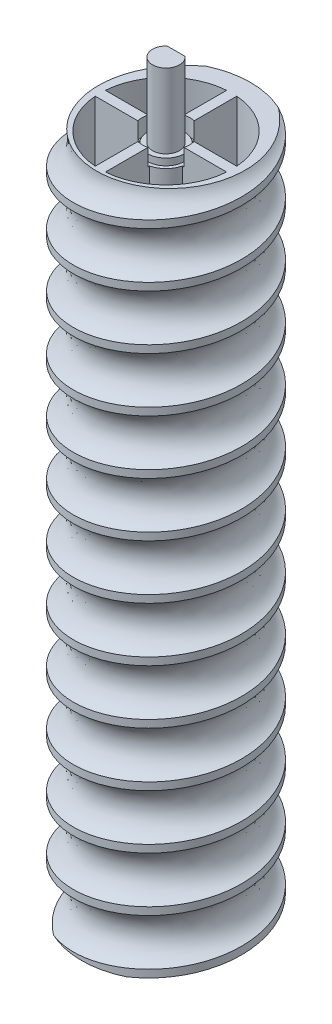
SolidWorks part; units mm, degrees
material "PMMA"
ref_plane "Front Plane" through (0, 0, 0) normal (0, 0, 1) x (1, 0, 0)
ref_plane "Top Plane" through (0, 0, 0) normal (0, 1, 0) x (1, 0, 0)
ref_plane "Right Plane" through (0, 0, 0) normal (1, 0, 0) x (0, 0, -1)
sketch "Sketch1" plane through (0, 0, 0) normal (0, 1, 0) x (1, 0, 0)
  circle A0 centre (0, 0) radius 25
  dimension "D1" = 50
extrude "Boss-Extrude1" add sketch "Sketch1" along normal blind 200
sketch "Sketch3" plane through (0, 200, 0) normal (0, 1, 0) x (1, 0, 0)
  circle A0 centre (0, 0) radius 25
  dimension "D1" = 50
curve "Helix/Spiral1" pitch 16 height 240 turns 15
sketch "Sketch4" plane through (0, 0, 0) normal (1, 0, 0) x (0, 0, -1)
  line L0 (-25, 200) -> (-43.3901, 200) construction
  circle A1 centre (-28, 200) radius 7.5
  dimension "D1" = 15
  dimension "D2" = 3
sweep "Cut-Sweep1" cut profiles "Sketch4" path "Helix/Spiral1"
sketch "Sketch5" plane through (0, 200, 0) normal (0, 1, 0) x (1, 0, 0)
  line L0 (0, 16.7786) -> (0, -20.3275) construction
  line L1 (-1.5, 19.4422) -> (-1.5, 6.3246)
  line L2 (1.5, 19.4422) -> (1.5, 6.3246)
  line L3 (19.4422, 1.5) -> (6.3246, 1.5)
  line L4 (19.4422, -1.5) -> (6.3246, -1.5)
  line L5 (1.5, -19.4422) -> (1.5, -6.3246)
  line L6 (-1.5, -19.4422) -> (-1.5, -6.3246)
  line L7 (-19.4422, -1.5) -> (-6.3246, -1.5)
  line L8 (-19.4422, 1.5) -> (-6.3246, 1.5)
  circle A0 centre (0, 0) radius 5
  arc A1 (-1.5, 19.4422) -> (-19.4422, 1.5) centre (0, 0) ccw
  arc A2 (-1.5, 6.3246) -> (-6.3246, 1.5) centre (0, 0) ccw
  arc A3 (-6.3246, -1.5) -> (-1.5, -6.3246) centre (0, 0) ccw
  arc A4 (-19.4422, -1.5) -> (-1.5, -19.4422) centre (0, 0) ccw
  arc A5 (19.4422, 1.5) -> (1.5, 19.4422) centre (0, 0) ccw
  arc A6 (6.3246, 1.5) -> (1.5, 6.3246) centre (0, 0) ccw
  arc A7 (1.5, -19.4422) -> (19.4422, -1.5) centre (0, 0) ccw
  arc A8 (1.5, -6.3246) -> (6.3246, -1.5) centre (0, 0) ccw
  point P26 (0, 0)
  dimension "D1" = 10
  dimension "D2" = 39
  dimension "D3" = 13
  dimension "D4" = 1.5
  dimension "D5" = 1.5
  dimension "D6" = 4
extrude "Cut-Extrude1" cut sketch "Sketch5" against normal through all
ref_plane "Plane1" through (0, 190, 0) normal (0, 1, 0) x (1, 0, 0)
sketch "Sketch6" plane through (0, 190, 0) normal (0, 1, 0) x (1, 0, 0)
  circle A0 centre (0, 0) radius 4
  dimension "D1" = 8
extrude "Boss-Extrude2" add sketch "Sketch6" along normal blind 29
sketch "Sketch7" plane through (0, 219, 0) normal (0, 1, 0) x (1, 0, 0)
  line L0 (-5.7944, 0) -> (5.9458, 0) construction
  line L2 (-2.6458, 3) -> (2.6458, 3)
  line L4 (-5.7944, 3) -> (5.9458, 3) construction
  arc A2 (2.6458, 3) -> (-2.6458, 3) centre (0, 0) ccw
  point P6 (-5.7944, 4)
  point P7 (5.9458, 4)
  dimension "D1" = 8
  dimension "D2" = 3
extrude "Cut-Extrude2" cut sketch "Sketch7" against normal blind 14
sketch "Sketch15" plane through (0, 0, 0) normal (0, -1, 0) x (1, 0, 0)
  circle A0 centre (0, 0) radius 5
  circle A1 centre (0, 0) radius 1.95
  dimension "D1" = 10
  dimension "D2" = 3.9
extrude "Boss-Extrude6" add sketch "Sketch15" along normal blind 1 and the other way blind 5
sketch "Sketch16" plane through (0, 200, 0) normal (0, 1, 0) x (1, 0, 0)
  circle A0 centre (0, 0) radius 5
  circle A1 centre (0, 0) radius 7
  dimension "D1" = 10
  dimension "D2" = 14
extrude "Cut-Extrude4" cut sketch "Sketch16" against normal blind 5
sketch "Sketch17" plane through (0, 195, 0) normal (0, 1, 0) x (1, 0, 0)
  circle A0 centre (0, 0) radius 5.5
  dimension "D1" = 11
extrude "Boss-Extrude7" add sketch "Sketch17" along normal blind 2
sketch "Sketch19" plane through (0, 219, 0) normal (0, 1, 0) x (1, 0, 0)
  circle A0 centre (0, 0) radius 3
  dimension "D1" = 6
extrude "Cut-Extrude5" cut sketch "Sketch19" against normal blind 50
sketch "Sketch20" plane through (0, -1, 0) normal (0, -1, 0) x (1, 0, 0)
  circle A0 centre (0, 0) radius 1.95
  circle A1 centre (0, 0) radius 5
  dimension "D1" = 3.9
  dimension "D2" = 10
extrude "Cut-Extrude6" cut sketch "Sketch20" against normal blind 2
sketch "Sketch21" plane through (0, 197, 0) normal (0, 1, 0) x (1, 0, 0)
  circle A0 centre (0, 0) radius 5.5
  dimension "D1" = 11
extrude "Boss-Extrude8" add sketch "Sketch21" against normal blind 7
